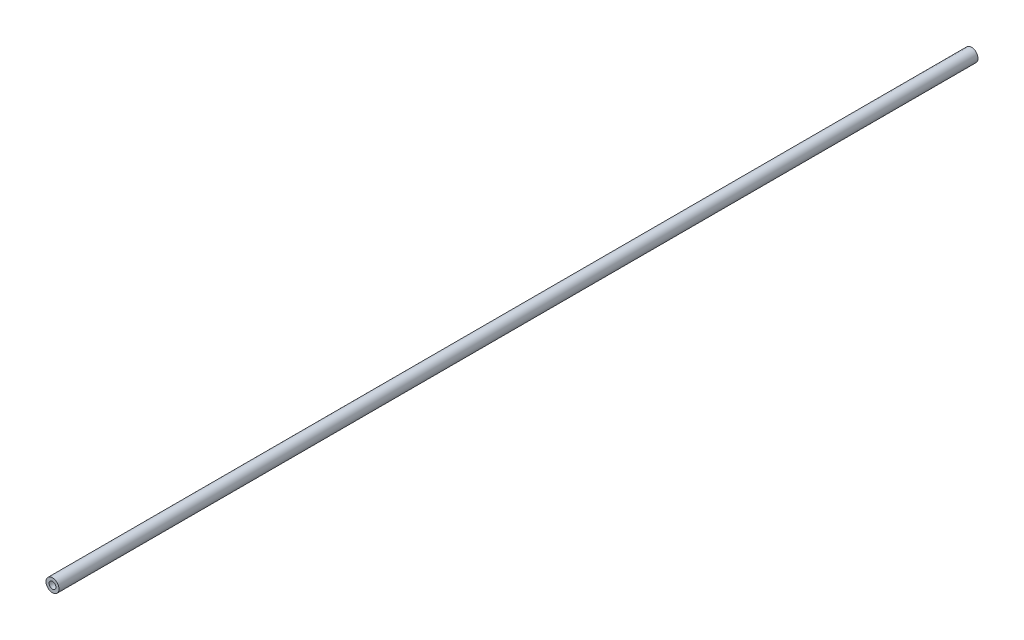
SolidWorks part; units mm, degrees
material "6061-T6 (SS)"
ref_plane "Front Plane" through (0, 0, 0) normal (0, 0, 1) x (1, 0, 0)
ref_plane "Top Plane" through (0, 0, 0) normal (0, 1, 0) x (1, 0, 0)
ref_plane "Right Plane" through (0, 0, 0) normal (1, 0, 0) x (0, 0, -1)
sketch "Sketch1" plane through (0, 0, 0) normal (0, 0, 1) x (1, 0, 0)
  circle A0 centre (0, 0) radius 4.7625
  circle A1 centre (0, 0) radius 2.4892
  dimension "D1" = 9.525
  dimension "D2" = 4.9784
extrude "Boss-Extrude1" add sketch "Sketch1" against normal blind 673.1
